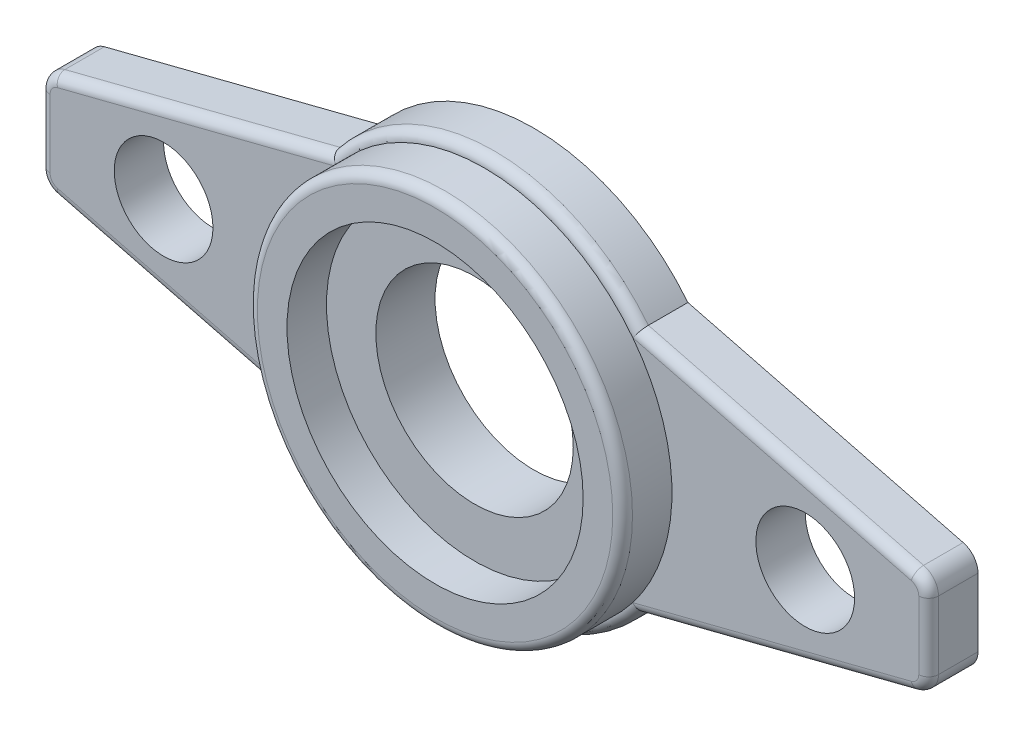
SolidWorks part; units mm, degrees
material "1060 Alloy"
ref_plane "Front Plane" through (0, 0, 0) normal (0, 0, 1) x (1, 0, 0)
ref_plane "Top Plane" through (0, 0, 0) normal (0, 1, 0) x (1, 0, 0)
ref_plane "Right Plane" through (0, 0, 0) normal (1, 0, 0) x (0, 0, -1)
sketch "Sketch2" plane through (0, 0, 0) normal (0, 0, 1) x (1, 0, 0)
  line L0 (-45, 0) -> (45, 0) construction
  line L1 (45, 3.4463) -> (45, -3.4463)
  line L2 (43.4946, -5.3842) -> (15.6125, -12.5)
  line L3 (0, 0) -> (0, 20) construction
  line L4 (43.4946, 5.3842) -> (15.6125, 12.5)
  line L5 (43.4946, -5.3842) -> (15.6125, -12.5)
  line L6 (43.4946, 5.3842) -> (15.6125, 12.5)
  line L7 (43.4946, -5.3842) -> (15.6125, -12.5)
  line L8 (43.4946, 5.3842) -> (15.6125, 12.5)
  line L9 (43.4946, -5.3842) -> (15.6125, -12.5)
  line L10 (43.4946, 5.3842) -> (15.6125, 12.5)
  line L11 (43.4946, -5.3842) -> (15.6125, -12.5)
  line L12 (43.4946, 5.3842) -> (15.6125, 12.5)
  line L13 (43.4946, -5.3842) -> (15.6125, -12.5)
  line L14 (43.4946, 5.3842) -> (15.6125, 12.5)
  line L15 (43.4946, -5.3842) -> (15.6125, -12.5)
  line L16 (43.4946, 5.3842) -> (15.6125, 12.5)
  line L17 (43.4946, -5.3842) -> (15.6125, -12.5)
  line L18 (43.4946, 5.3842) -> (15.6125, 12.5)
  line L19 (43.4946, -5.3842) -> (15.6125, -12.5)
  line L20 (43.4946, 5.3842) -> (15.6125, 12.5)
  line L21 (43.4946, -5.3842) -> (15.6125, -12.5)
  line L22 (43.4946, 5.3842) -> (15.6125, 12.5)
  line L23 (43.4946, -5.3842) -> (15.6125, -12.5)
  line L24 (43.4946, 5.3842) -> (15.6125, 12.5)
  line L25 (43.4946, -5.3842) -> (15.6125, -12.5)
  line L26 (43.4946, 5.3842) -> (15.6125, 12.5)
  line L27 (43.4946, -5.3842) -> (15.6125, -12.5)
  line L28 (43.4946, 5.3842) -> (15.6125, 12.5)
  line L29 (43.4946, -5.3842) -> (15.6125, -12.5)
  line L30 (43.4946, 5.3842) -> (15.6125, 12.5)
  line L31 (43.4946, -5.3842) -> (15.6125, -12.5)
  line L32 (43.4946, 5.3842) -> (15.6125, 12.5)
  line L33 (43.4946, -5.3842) -> (15.6125, -12.5)
  line L34 (43.4946, 5.3842) -> (15.6125, 12.5)
  line L35 (-43.4946, 5.3842) -> (-15.6125, 12.5)
  line L36 (-43.4946, -5.3842) -> (-15.6125, -12.5)
  line L37 (-43.4946, 5.3842) -> (-15.6125, 12.5)
  line L38 (-43.4946, -5.3842) -> (-15.6125, -12.5)
  line L39 (-43.4946, 5.3842) -> (-15.6125, 12.5)
  line L40 (-43.4946, -5.3842) -> (-15.6125, -12.5)
  line L41 (-43.4946, 5.3842) -> (-15.6125, 12.5)
  line L42 (-43.4946, -5.3842) -> (-15.6125, -12.5)
  line L43 (-43.4946, 5.3842) -> (-15.6125, 12.5)
  line L44 (-43.4946, -5.3842) -> (-15.6125, -12.5)
  line L45 (-43.4946, 5.3842) -> (-15.6125, 12.5)
  line L46 (-43.4946, -5.3842) -> (-15.6125, -12.5)
  line L47 (-43.4946, 5.3842) -> (-15.6125, 12.5)
  line L48 (-43.4946, -5.3842) -> (-15.6125, -12.5)
  line L49 (-43.4946, 5.3842) -> (-15.6125, 12.5)
  line L50 (-43.4946, -5.3842) -> (-15.6125, -12.5)
  line L51 (-43.4946, 5.3842) -> (-15.6125, 12.5)
  line L52 (-43.4946, -5.3842) -> (-15.6125, -12.5)
  line L53 (-43.4946, 5.3842) -> (-15.6125, 12.5)
  line L54 (-43.4946, -5.3842) -> (-15.6125, -12.5)
  line L55 (-43.4946, 5.3842) -> (-15.6125, 12.5)
  line L56 (-43.4946, -5.3842) -> (-15.6125, -12.5)
  line L57 (-43.4946, 5.3842) -> (-15.6125, 12.5)
  line L58 (-43.4946, -5.3842) -> (-15.6125, -12.5)
  line L59 (-43.4946, 5.3842) -> (-15.6125, 12.5)
  line L60 (-43.4946, -5.3842) -> (-15.6125, -12.5)
  line L61 (-43.4946, 5.3842) -> (-15.6125, 12.5)
  line L62 (-43.4946, -5.3842) -> (-15.6125, -12.5)
  line L63 (-43.4946, 5.3842) -> (-15.6125, 12.5)
  line L64 (-43.4946, -5.3842) -> (-15.6125, -12.5)
  line L65 (-43.4946, 5.3842) -> (-15.6125, 12.5)
  line L66 (-43.4946, -5.3842) -> (-15.6125, -12.5)
  line L67 (-45, 3.4463) -> (-45, -3.4463)
  circle A0 centre (0, 0) radius 20
  circle A1 centre (0, 0) radius 19
  circle A2 centre (0, 0) radius 15
  circle A3 centre (0, 0) radius 10
  circle A4 centre (32.5, 0) radius 5
  arc A5 (45, -3.4463) -> (43.4946, -5.3842) centre (43, -3.4463) cw
  arc A6 (45, 3.4463) -> (43.4946, 5.3842) centre (43, 3.4463) ccw
  arc A7 (45, -3.4463) -> (43.4946, -5.3842) centre (43, -3.4463) cw
  arc A8 (45, 3.4463) -> (43.4946, 5.3842) centre (43, 3.4463) ccw
  arc A9 (45, -3.4463) -> (43.4946, -5.3842) centre (43, -3.4463) cw
  arc A10 (45, 3.4463) -> (43.4946, 5.3842) centre (43, 3.4463) ccw
  arc A11 (45, -3.4463) -> (43.4946, -5.3842) centre (43, -3.4463) cw
  arc A12 (45, 3.4463) -> (43.4946, 5.3842) centre (43, 3.4463) ccw
  arc A13 (45, -3.4463) -> (43.4946, -5.3842) centre (43, -3.4463) cw
  arc A14 (45, 3.4463) -> (43.4946, 5.3842) centre (43, 3.4463) ccw
  arc A15 (45, -3.4463) -> (43.4946, -5.3842) centre (43, -3.4463) cw
  arc A16 (45, 3.4463) -> (43.4946, 5.3842) centre (43, 3.4463) ccw
  arc A17 (45, -3.4463) -> (43.4946, -5.3842) centre (43, -3.4463) cw
  arc A18 (45, 3.4463) -> (43.4946, 5.3842) centre (43, 3.4463) ccw
  arc A19 (45, -3.4463) -> (43.4946, -5.3842) centre (43, -3.4463) cw
  arc A20 (45, 3.4463) -> (43.4946, 5.3842) centre (43, 3.4463) ccw
  arc A21 (45, -3.4463) -> (43.4946, -5.3842) centre (43, -3.4463) cw
  arc A22 (45, 3.4463) -> (43.4946, 5.3842) centre (43, 3.4463) ccw
  arc A23 (45, -3.4463) -> (43.4946, -5.3842) centre (43, -3.4463) cw
  arc A24 (45, 3.4463) -> (43.4946, 5.3842) centre (43, 3.4463) ccw
  arc A25 (45, -3.4463) -> (43.4946, -5.3842) centre (43, -3.4463) cw
  arc A26 (45, 3.4463) -> (43.4946, 5.3842) centre (43, 3.4463) ccw
  arc A27 (45, -3.4463) -> (43.4946, -5.3842) centre (43, -3.4463) cw
  arc A28 (45, 3.4463) -> (43.4946, 5.3842) centre (43, 3.4463) ccw
  arc A29 (45, -3.4463) -> (43.4946, -5.3842) centre (43, -3.4463) cw
  arc A30 (45, 3.4463) -> (43.4946, 5.3842) centre (43, 3.4463) ccw
  arc A31 (45, -3.4463) -> (43.4946, -5.3842) centre (43, -3.4463) cw
  arc A32 (45, 3.4463) -> (43.4946, 5.3842) centre (43, 3.4463) ccw
  arc A33 (45, -3.4463) -> (43.4946, -5.3842) centre (43, -3.4463) cw
  arc A34 (45, 3.4463) -> (43.4946, 5.3842) centre (43, 3.4463) ccw
  arc A35 (45, -3.4463) -> (43.4946, -5.3842) centre (43, -3.4463) cw
  arc A36 (45, 3.4463) -> (43.4946, 5.3842) centre (43, 3.4463) ccw
  arc A37 (-45, 3.4463) -> (-43.4946, 5.3842) centre (-43, 3.4463) cw
  arc A38 (-45, -3.4463) -> (-43.4946, -5.3842) centre (-43, -3.4463) ccw
  arc A39 (-45, 3.4463) -> (-43.4946, 5.3842) centre (-43, 3.4463) cw
  arc A40 (-45, -3.4463) -> (-43.4946, -5.3842) centre (-43, -3.4463) ccw
  arc A41 (-45, 3.4463) -> (-43.4946, 5.3842) centre (-43, 3.4463) cw
  arc A42 (-45, -3.4463) -> (-43.4946, -5.3842) centre (-43, -3.4463) ccw
  arc A43 (-45, 3.4463) -> (-43.4946, 5.3842) centre (-43, 3.4463) cw
  arc A44 (-45, -3.4463) -> (-43.4946, -5.3842) centre (-43, -3.4463) ccw
  arc A45 (-45, 3.4463) -> (-43.4946, 5.3842) centre (-43, 3.4463) cw
  arc A46 (-45, -3.4463) -> (-43.4946, -5.3842) centre (-43, -3.4463) ccw
  arc A47 (-45, 3.4463) -> (-43.4946, 5.3842) centre (-43, 3.4463) cw
  arc A48 (-45, -3.4463) -> (-43.4946, -5.3842) centre (-43, -3.4463) ccw
  arc A49 (-45, 3.4463) -> (-43.4946, 5.3842) centre (-43, 3.4463) cw
  arc A50 (-45, -3.4463) -> (-43.4946, -5.3842) centre (-43, -3.4463) ccw
  arc A51 (-45, 3.4463) -> (-43.4946, 5.3842) centre (-43, 3.4463) cw
  arc A52 (-45, -3.4463) -> (-43.4946, -5.3842) centre (-43, -3.4463) ccw
  arc A53 (-45, 3.4463) -> (-43.4946, 5.3842) centre (-43, 3.4463) cw
  arc A54 (-45, -3.4463) -> (-43.4946, -5.3842) centre (-43, -3.4463) ccw
  arc A55 (-45, 3.4463) -> (-43.4946, 5.3842) centre (-43, 3.4463) cw
  arc A56 (-45, -3.4463) -> (-43.4946, -5.3842) centre (-43, -3.4463) ccw
  arc A57 (-45, 3.4463) -> (-43.4946, 5.3842) centre (-43, 3.4463) cw
  arc A58 (-45, -3.4463) -> (-43.4946, -5.3842) centre (-43, -3.4463) ccw
  arc A59 (-45, 3.4463) -> (-43.4946, 5.3842) centre (-43, 3.4463) cw
  arc A60 (-45, -3.4463) -> (-43.4946, -5.3842) centre (-43, -3.4463) ccw
  arc A61 (-45, 3.4463) -> (-43.4946, 5.3842) centre (-43, 3.4463) cw
  arc A62 (-45, -3.4463) -> (-43.4946, -5.3842) centre (-43, -3.4463) ccw
  arc A63 (-45, 3.4463) -> (-43.4946, 5.3842) centre (-43, 3.4463) cw
  arc A64 (-45, -3.4463) -> (-43.4946, -5.3842) centre (-43, -3.4463) ccw
  arc A65 (-45, 3.4463) -> (-43.4946, 5.3842) centre (-43, 3.4463) cw
  arc A66 (-45, -3.4463) -> (-43.4946, -5.3842) centre (-43, -3.4463) ccw
  arc A67 (-45, 3.4463) -> (-43.4946, 5.3842) centre (-43, 3.4463) cw
  arc A68 (-45, -3.4463) -> (-43.4946, -5.3842) centre (-43, -3.4463) ccw
  circle A69 centre (-32.5, 0) radius 5
  point P14 (45, -5)
  point P20 (45, 5)
  point P32 (-45, 5)
  point P33 (-45, -5)
  dimension "D1" = 38
  dimension "D2" = 40
  dimension "D3" = 4
  dimension "D4" = 20
  dimension "D8" = 10
  dimension "D10" = 2
  dimension "D5" = 45
  dimension "D6" = 5
  dimension "D7" = 12.5
  dimension "D9" = 12.5
extrude "Boss-Extrude1" add sketch "Sketch2" along normal blind 5 contours L67 A38 L36 A0 L35 A37 A69 | A0 A1 | L1 A6 L4 A0 L2 A5 A4 region at (44.6142, 0, 0) region at (18.3375, 6.4365, 0) region at (-20.3858, 0, 0)
extrude "Boss-Extrude2" add sketch "Sketch2<3>" along normal blind 10 contours A1 A2 region at (-18.4626, 0, 0)
sketch "Sketch2<3>" plane through (0, 0, 0) normal (0, 0, 1) x (1, 0, 0) same geometry as "Sketch2"
extrude "Boss-Extrude3" add sketch "Sketch2<4>" along normal blind 6 contours A2 A3 region at (-14.5757, 0, 0)
sketch "Sketch2<4>" plane through (0, 0, 0) normal (0, 0, 1) x (1, 0, 0) same geometry as "Sketch2"
fillet "Fillet1" radius 1 1 edges at (19, 0, 10)
fillet "Fillet2" radius 1 12 edges at (29.5535, 8.9421, 5) (44.5794, 4.6733, 5) (45, 0, 5) (44.5794, -4.6733, 5) (-29.5535, 8.9421, 5) (-44.5794, 4.6733, 5) (-45, 0, 5) (-44.5794, -4.6733, 5) (0, 20, 5) (29.5535, -8.9421, 5) (-29.5535, -8.9421, 5) (0, -20, 5)
